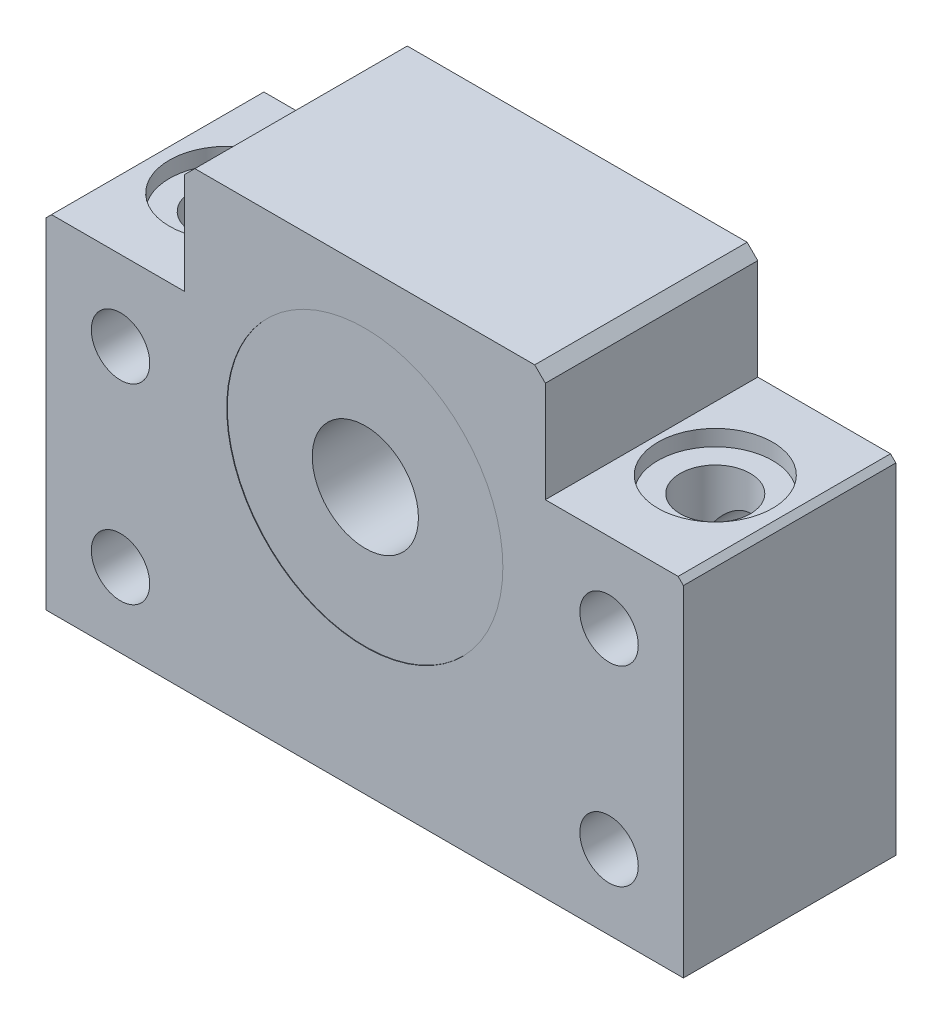
SolidWorks part; units mm, degrees
material "6061-T6 (SS)"
ref_plane "Спереди" through (0, 0, 0) normal (0, 0, 1) x (1, 0, 0)
ref_plane "Сверху" through (0, 0, 0) normal (0, 1, 0) x (1, 0, 0)
ref_plane "Справа" through (0, 0, 0) normal (1, 0, 0) x (0, 0, -1)
sketch "Эскиз1" plane through (0, 0, 0) normal (0, 0, 1) x (1, 0, 0)
  line L0 (-30, -25) -> (-30, 7)
  line L1 (0, -25) -> (0, 18) construction
  line L2 (-30, -25) -> (30, -25)
  line L3 (-29.5, 7.5) -> (-17, 7.5)
  line L4 (17, 17) -> (17, 7.5)
  line L5 (-27.8123, 0) -> (-18.3765, 0) construction
  line L6 (-23, -25) -> (-23, 7.5) construction
  line L7 (-18.3765, -18) -> (-27.8123, -18) construction
  line L8 (18.3765, -18) -> (27.8123, -18) construction
  line L9 (23, -25) -> (23, 7.5) construction
  line L10 (27.8123, 0) -> (18.3765, 0) construction
  line L11 (-16, 18) -> (-17, 17)
  line L12 (29.5, 7.5) -> (17, 7.5)
  line L13 (30, -25) -> (30, 7)
  line L14 (16, 18) -> (-16, 18)
  line L15 (-30, 7) -> (-29.5, 7.5)
  line L16 (-17, 17) -> (-17, 7.5)
  line L17 (16, 18) -> (17, 17)
  line L18 (30, 7) -> (29.5, 7.5)
  circle A0 centre (-23, 0) radius 2.75
  circle A1 centre (-23, -18) radius 2.75
  circle A2 centre (23, -18) radius 2.75
  circle A3 centre (23, 0) radius 2.75
  circle A4 centre (0, 0) radius 13
  point P1 (-30, 7.5)
  point P8 (17, 18)
  point P29 (30, 7.5)
  point P36 (-17, 18)
  dimension "D1" = 60
  dimension "D2" = 46
  dimension "D8" = 5.5
  dimension "D3" = 30
  dimension "D4" = 18
  dimension "D5" = 25
  dimension "D6" = 32.5
  dimension "D7" = 43
  dimension "D9" = 34
extrude "Бобышка-Вытянуть1" add sketch "Эскиз1" along normal blind 10 and the other way blind 10
sketch "Эскиз2" plane through (0, 0, 0) normal (0, 1, 0) x (1, 0, 0)
  line L0 (29.5, -10) -> (17, -10) construction
  line L1 (-23, 10) -> (-23, -10) construction
  line L2 (-30, 0) -> (30, 0) construction
  line L8 (23, 10) -> (23, -10) construction
  circle A0 centre (-23, 0) radius 3.3
  circle A1 centre (23, 0) radius 3.3
  point P10 (30, -6.5545)
  dimension "D1" = 46
  dimension "D2" = 10
extrude "Вырез-Вытянуть1" cut sketch "Эскиз2" against normal through all from offset 7.5
sketch "Эскиз3" plane through (0, 0, 0) normal (0, 1, 0) x (1, 0, 0)
  circle A0 centre (-23, 0) radius 5.4
  circle A1 centre (23, 0) radius 5.4
extrude "Вырез-Вытянуть2" cut sketch "Эскиз3" against normal blind 1.5 from offset 7.5
sketch "Эскиз4" plane through (0, 0, 0) normal (0, 0, 1) x (1, 0, 0)
  circle A0 centre (0, 0) radius 13
  circle A1 centre (0, 0) radius 5
extrude "Бобышка-Вытянуть2" add sketch "Эскиз4" along normal blind 4 and the other way blind 4 from offset 5.95
